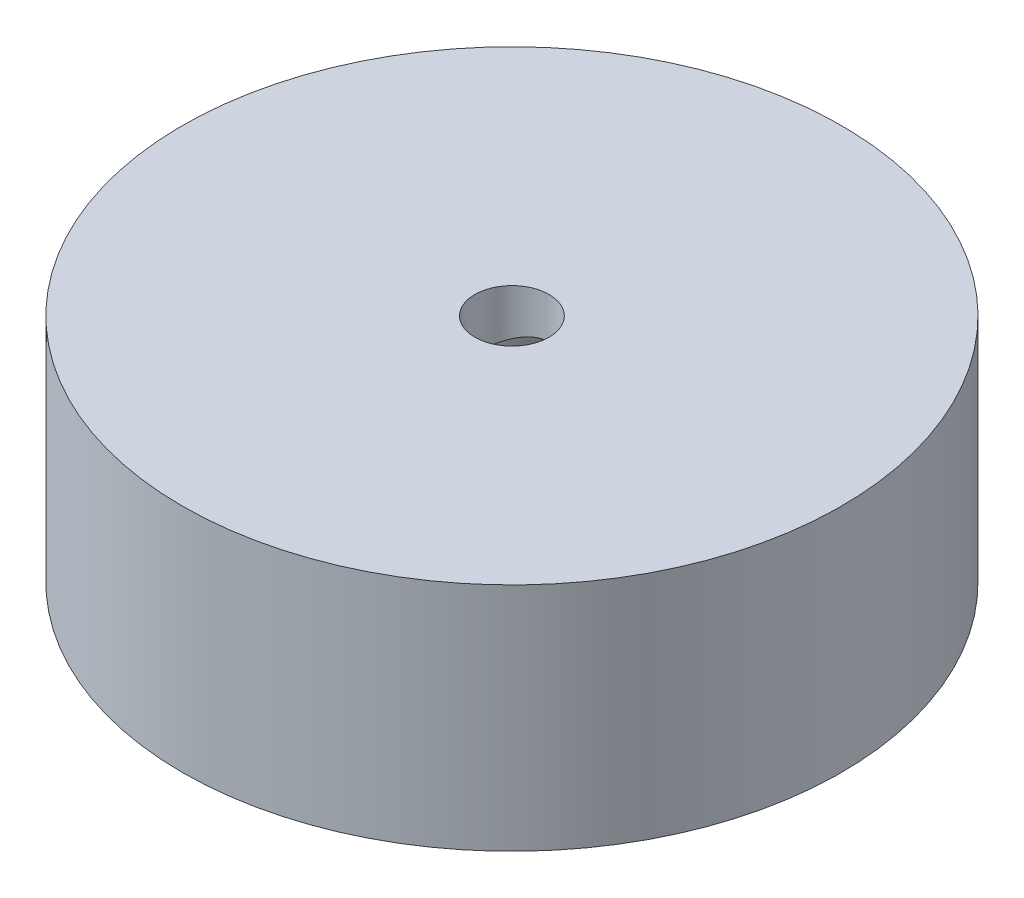
SolidWorks part; units mm, degrees
ref_plane "Front Plane" through (0, 0, 0) normal (0, 0, 1) x (1, 0, 0)
ref_plane "Top Plane" through (0, 0, 0) normal (0, 1, 0) x (1, 0, 0)
ref_plane "Right Plane" through (0, 0, 0) normal (1, 0, 0) x (0, 0, -1)
sketch "Sketch1" plane through (0, 0, 0) normal (0, 1, 0) x (1, 0, 0)
  circle A0 centre (0, 0) radius 1.125
  circle A1 centre (0, 0) radius 10
  dimension "D1" = 2.25
  dimension "D2" = 20
extrude "Boss-Extrude1" add sketch "Sketch1" along normal blind 3.5 and the other way blind 3.5
sketch "Sketch12" plane through (0, 0, 0) normal (0, 1, 0) x (1, 0, 0)
  line L0 (-2.25, 1.625) -> (-2.25, 0.625)
  line L2 (-2.25, 0.625) -> (-1.25, 1.125)
  line L3 (-2.25, 1.125) -> (-1.25, 1.125) construction
  line L4 (-2.25, 1.625) -> (-1.25, 1.125)
  circle A1 centre (0, 0) radius 1.125 construction
  dimension "D1" = 1
  dimension "D2" = 0.5
  dimension "D3" = 2.25
sketch "Sketch13" plane through (0, 0, 0) normal (0, 0, 1) x (1, 0, 0)
  circle A0 centre (0, 0) radius 2.25
  dimension "D1" = 4.5
extrude "Cut-Extrude2" cut sketch "Sketch13" against normal blind 13
ref_plane "Plane3" through (0, 0, -1.125) normal (0, 0, 1) x (1, 0, 0)
sketch "Sketch14" plane through (0, 0, -1.125) normal (0, 0, 1) x (1, 0, 0)
  circle A0 centre (0, 0) radius 2.5
  dimension "D1" = 5
curve "Helix/Spiral3" pitch 2 height 8 radius 2.5 centre (0, 0, -1.125) axis (0, 0, -1) start towards (-1, 0, 0)
sweep "Sweep2" add profiles "Sketch12" path "Helix/Spiral3"
